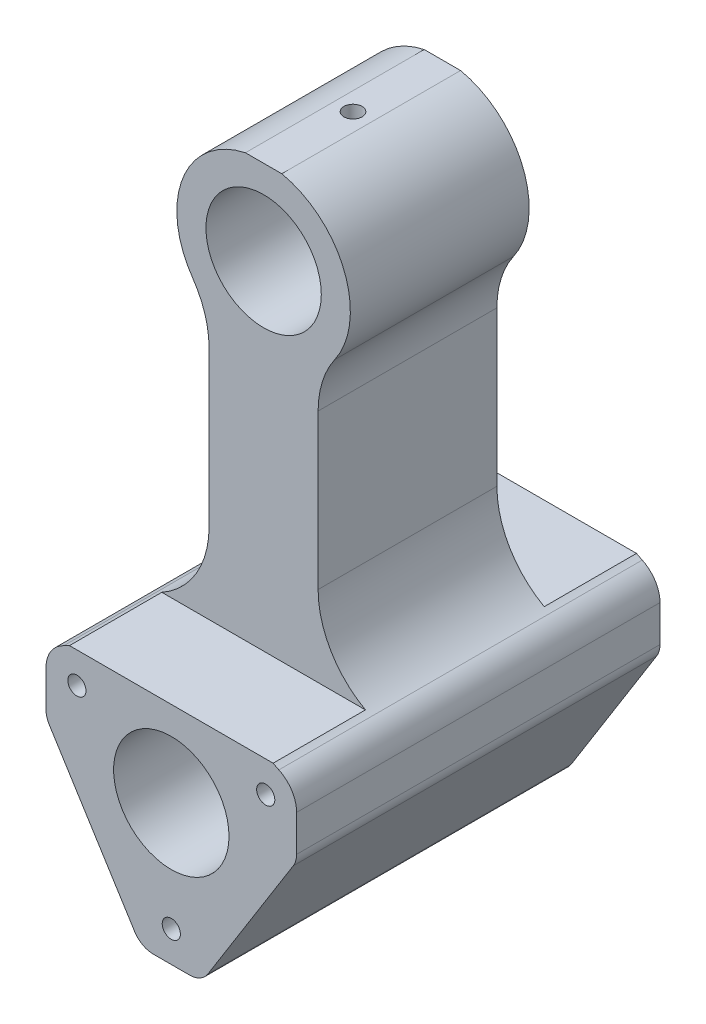
SolidWorks part; units mm, degrees
material "6061-T6 (SS)"
ref_plane "Front Plane" through (0, 0, 0) normal (0, 0, 1) x (1, 0, 0)
ref_plane "Top Plane" through (0, 0, 0) normal (0, 1, 0) x (1, 0, 0)
ref_plane "Right Plane" through (0, 0, 0) normal (1, 0, 0) x (0, 0, -1)
sketch "Sketch1" plane through (0, 0, 0) normal (0, 0, 1) x (1, 0, 0)
  line L9 (-14.0116, -46.4632) -> (14.0116, -46.4632)
  line L15 (-17.2404, -50.7132) -> (-17.2404, -55.7132)
  line L24 (-7.5, -14.1055) -> (-7.5, -35.3729)
  line L25 (7.5, -14.1055) -> (7.5, -35.3729)
  line L27 (-12.9904, -50.7132) -> (0, -58.2132) construction
  line L28 (0, -58.2132) -> (12.9904, -50.7132) construction
  line L29 (0, -73.2132) -> (0, -58.2132) construction
  line L30 (17.2404, -50.7132) -> (17.2404, -55.7132)
  line L32 (-16.7831, -57.3053) -> (-5.0427, -76.0553)
  line L33 (16.7831, -57.3053) -> (5.0427, -76.0553)
  line L34 (2.5, -77.4632) -> (-2.5, -77.4632)
  line L35 (-2.5, 11.6728) -> (2.5, 11.6728)
  circle A0 centre (0, 0) radius 7.9375
  arc A13 (17.2404, -55.7132) -> (16.7831, -57.3053) centre (14.2404, -55.7132) cw
  arc A14 (-17.2404, -55.7132) -> (-16.7831, -57.3053) centre (-14.2404, -55.7132) ccw
  arc A18 (-2.5, -77.4632) -> (-5.0427, -76.0553) centre (-2.5, -74.4632) cw
  arc A19 (2.5, -77.4632) -> (5.0427, -76.0553) centre (2.5, -74.4632) ccw
  arc A20 (2.5, 11.6728) -> (9.7874, -6.8345) centre (0, 0) cw
  arc A26 (-9.7874, -6.8345) -> (-2.5, 11.6728) centre (0, 0) cw
  arc A30 (-14.7981, -46.8668) -> (-17.2404, -50.7132) centre (-12.9904, -50.7132) ccw
  circle A31 centre (0, -73.2132) radius 4.25 construction
  arc A32 (17.2404, -50.7132) -> (14.7981, -46.8668) centre (12.9904, -50.7132) ccw
  circle A33 centre (0, -73.2132) radius 1.65 construction
  circle A34 centre (12.9904, -50.7132) radius 1.65 construction
  circle A35 centre (-12.9904, -50.7132) radius 1.25 construction
  circle A36 centre (12.9904, -50.7132) radius 1.25 construction
  circle A37 centre (0, -73.2132) radius 1.25 construction
  arc A38 (-7.5, -35.3729) -> (-14.7981, -46.8668) centre (-20.2, -35.3729) cw
  arc A39 (7.5, -35.3729) -> (14.7981, -46.8668) centre (20.2, -35.3729) ccw
  arc A40 (9.7874, -6.8345) -> (7.5, -14.1055) centre (20.2, -14.1055) ccw
  arc A41 (-9.7874, -6.8345) -> (-7.5, -14.1055) centre (-20.2, -14.1055) cw
  circle A42 centre (0, -58.2132) radius 6.35 construction
  point P32 (7.5, -9.2873)
  point P35 (-7.5, -9.2873)
  point P43 (4.3702, 11.1088)
  point P48 (0, -77.4632)
  dimension "D1" = 15.875
  dimension "D2" = 2.5
  dimension "D4" = 4
  dimension "D8" = 12.7
  dimension "D9" = 5
  dimension "D11" = 3
  dimension "D3" = 3
  dimension "D5" = 12.7
  dimension "D7" = 12.7
  dimension "D10" = 5
  dimension "D6" = 15
  dimension "D12" = 5
extrude "Boss-Extrude1" add sketch "Sketch1" along normal mid plane 50 contours A39 A38 A30 A31 A32 A37 A36 A35 region at (0, -59.1245, 0)
extrude "Boss-Extrude2" add sketch "Sketch1<3>" along normal mid plane 24.6 contours A0 region at (0, -20.7723, 0)
sketch "Sketch1<3>" plane through (0, 0, 0) normal (0, 0, 1) x (1, 0, 0) same geometry as "Sketch1"
sketch "Sketch3" plane through (0, 0, 0) normal (0, 1, 0) x (1, 0, 0)
  circle A0 centre (0, 0) radius 1.25
  dimension "D1" = 2.5
extrude "Cut-Extrude1" cut sketch "Sketch3" along normal through all
sketch "Sketch4" plane through (0, 0, 25) normal (0, 0, 1) x (1, 0, 0)
  circle A0 centre (-12.9904, -50.7132) radius 1.25
  circle A1 centre (12.9904, -50.7132) radius 1.25
  circle A2 centre (0, -73.2132) radius 1.25
  dimension "D1" = 2.5
extrude "Cut-Extrude2" cut sketch "Sketch4" against normal blind 10
mirror "Mirror1" about plane through (0, 0, 0) normal (0, 0, 1) of "Cut-Extrude2"
sketch "Sketch5" plane through (0, 0, 25) normal (0, 0, 1) x (1, 0, 0)
  circle A7 centre (0, -58.2132) radius 13.75 construction
  circle A8 centre (-12.9904, -50.7132) radius 1.25 construction
  circle A9 centre (12.9904, -50.7132) radius 1.25 construction
  circle A10 centre (0, -73.2132) radius 1.25 construction
  circle A11 centre (0, -58.2132) radius 7.9375
  dimension "D1" = 15.875
extrude "Cut-Extrude3" cut sketch "Sketch5" against normal through all
